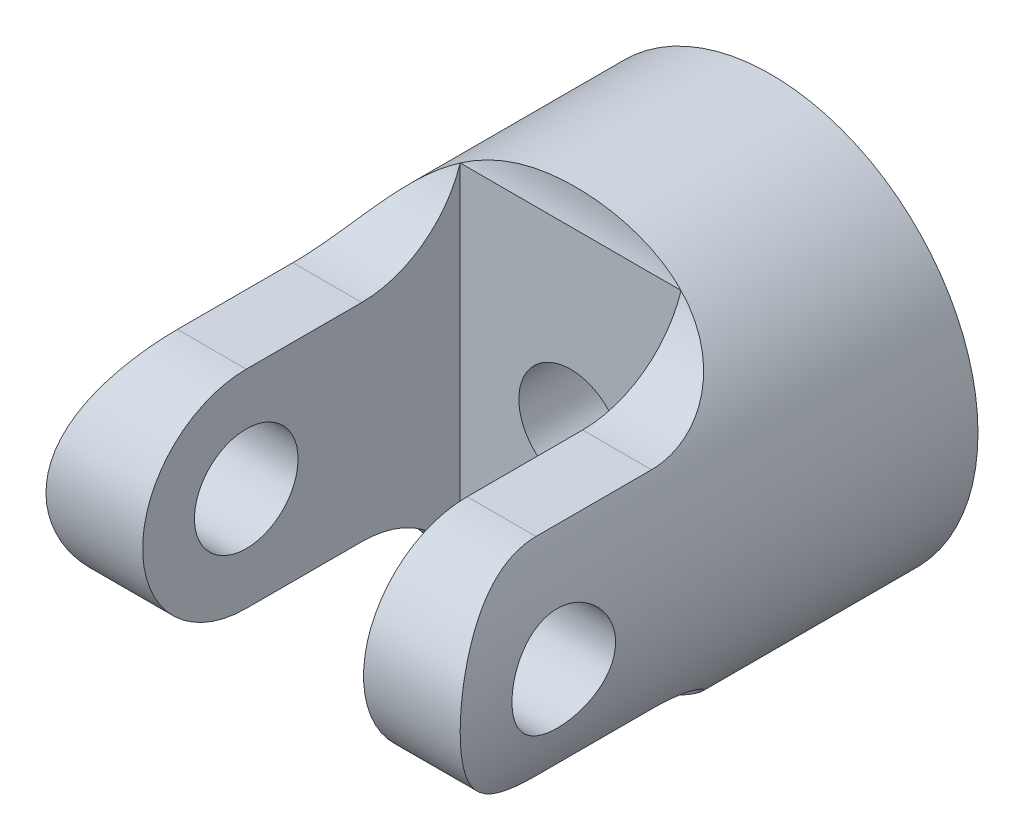
SolidWorks part; units mm, degrees
ref_plane "Front Plane" through (0, 0, 0) normal (0, 0, 1) x (1, 0, 0)
ref_plane "Top Plane" through (0, 0, 0) normal (0, 1, 0) x (1, 0, 0)
ref_plane "Right Plane" through (0, 0, 0) normal (1, 0, 0) x (0, 0, -1)
sketch "Sketch1" plane through (0, 0, 0) normal (0, 0, 1) x (1, 0, 0)
  circle A0 centre (0, 0) radius 19.05
  circle A1 centre (0, 0) radius 4.765
  dimension "D1" = 38.1
  dimension "D2" = 9.53
extrude "Boss-Extrude1" add sketch "Sketch1" along normal blind 47.63
sketch "Sketch2" plane through (0, 0, 0) normal (0, 1, 0) x (1, 0, 0)
  line L0 (-10.16, -47.63) -> (10.16, -47.63)
  line L1 (-10.16, -47.63) -> (-10.16, -18.42)
  line L2 (10.16, -47.63) -> (10.16, -18.42)
  line L3 (-10.16, -18.42) -> (10.16, -18.42)
  line L4 (-19.05, -47.63) -> (19.05, -47.63) construction
  line L6 (19.05, 0) -> (-19.05, 0) construction
  point P6 (12.9527, -24.157)
  dimension "D1" = 20.32
  dimension "D2" = 10.16
  dimension "D3" = 18.42
extrude "Cut-Extrude1" cut sketch "Sketch2" along normal through all both and the other way through all
sketch "Sketch3" plane through (0, 0, 0) normal (1, 0, 0) x (0, 0, -1)
  line L0 (0, 0) -> (-50000, 0) construction
  line L1 (-47.63, 16.1145) -> (-47.63, -16.1145) construction
  line L2 (-38.1, 9.53) -> (-24.7404, 9.53)
  line L4 (-38.1, -9.53) -> (-24.7404, -9.53)
  line L5 (-38.1, 9.53) -> (-55.8975, 9.53)
  line L6 (-55.8975, 9.53) -> (-47.498, 20.5756)
  line L7 (-47.498, 20.5756) -> (-17.9561, 19.05)
  line L8 (-55.8975, -9.53) -> (-47.498, -20.5756)
  line L9 (-38.1, -9.53) -> (-55.8975, -9.53)
  line L10 (-47.498, -20.5756) -> (-17.9561, -19.05)
  line L11 (-47.63, 0) -> (-47.63, 9.53)
  line L12 (-47.63, 0) -> (-47.63, -9.53)
  circle A0 centre (-38.1, 0) radius 4.765
  circle A1 centre (-38.1, 0) radius 9.53
  circle A2 centre (-27.4761, 19.05) radius 9.52
  circle A3 centre (-27.4761, -19.05) radius 9.52
  dimension "D1" = 9.53
  dimension "D2" = 19.06
extrude "Cut-Extrude3" cut sketch "Sketch3" against normal through all both and the other way through all contours A2 L7 L6 L5 L2 | L7 A2 | A1 L5 L11 | A1 L12 L9 | L10 A3 L4 L9 L8 | A3 L10 region at (0, 14.1222, 43.5592) region at (0, 7.4013, 45.5013) region at (0, 15.2786, 27.6709) region at (0, -7.4013, 45.5013) region at (0, -14.1222, 43.5592) region at (0, -15.2786, 27.6709)
extrude "Cut-Extrude4" cut sketch "Sketch3<5>" against normal through all both and the other way through all contours A0 L0 | L0 A0 region at (0, -2.0223, 38.1) region at (0, 2.0223, 38.1)
sketch "Sketch3<5>" plane through (0, 0, 0) normal (1, 0, 0) x (0, 0, -1) same geometry as "Sketch3"
